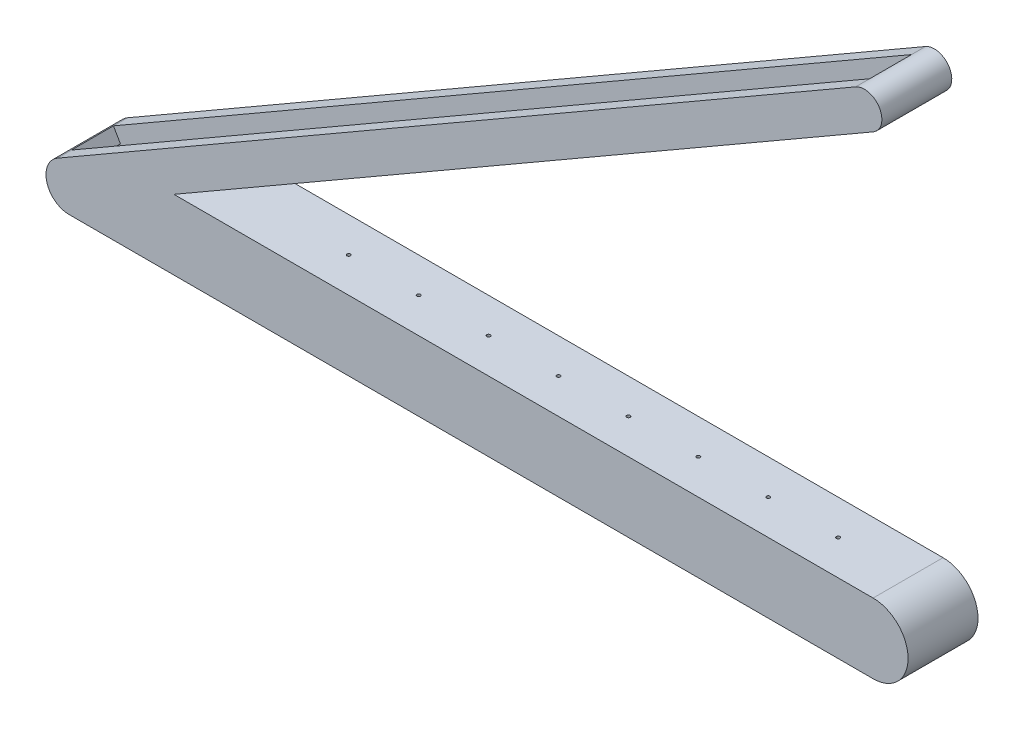
SolidWorks part; units mm, degrees
ref_plane "Front Plane" through (0, 0, 0) normal (0, 0, 1) x (1, 0, 0)
ref_plane "Top Plane" through (0, 0, 0) normal (0, 1, 0) x (1, 0, 0)
ref_plane "Right Plane" through (0, 0, 0) normal (1, 0, 0) x (0, 0, -1)
sketch "Sketch1" plane through (0, 0, 0) normal (0, 0, 1) x (1, 0, 0)
  line L0 (0, 0) -> (1000, 0)
  line L1 (0, 0) -> (1000, 577.3503)
  line L2 (1000, -100) -> (-150, -100)
  line L3 (-166.5064, -38.3975) -> (975, 620.6515)
  arc A1 (1000, 0) -> (1000, -100) centre (1000, -50) cw
  arc A3 (-166.5064, -38.3975) -> (-150, -100) centre (-150, -66.9873) ccw
  arc A4 (1000, 577.3503) -> (975, 620.6515) centre (987.5, 599.0009) ccw
  dimension "D1" = 50
  dimension "D2" = 100
  dimension "D3" = 1000
  dimension "D4" = 1150
  dimension "D5" = 30
extrude "Boss-Extrude1" add sketch "Sketch1" along normal blind 100
shell "Shell1" thickness 20 removed face at (404.2468, 291.127, 50) removed face at (425, -100, 50)
sketch "Sketch3" plane through (0, 0, 0) normal (0, 1, 0) x (1, 0, 0)
  line L0 (0, -1000) -> (0, 49000) construction
  line L1 (975, 0) -> (-166.5064, 0) construction
  circle A0 centre (200, -50) radius 2.5
  circle A1 centre (300, -50) radius 2.5
  circle A2 centre (400, -50) radius 2.5
  circle A3 centre (500, -50) radius 2.5
  circle A4 centre (600, -50) radius 2.5
  circle A5 centre (700, -50) radius 2.5
  circle A6 centre (800, -50) radius 2.5
  circle A7 centre (900, -50) radius 2.5
  dimension "D1" = 50
  dimension "D2" = 200
  dimension "D3" = 8
extrude "Cut-Extrude5" cut sketch "Sketch3" against normal through all and the other way blind 700
